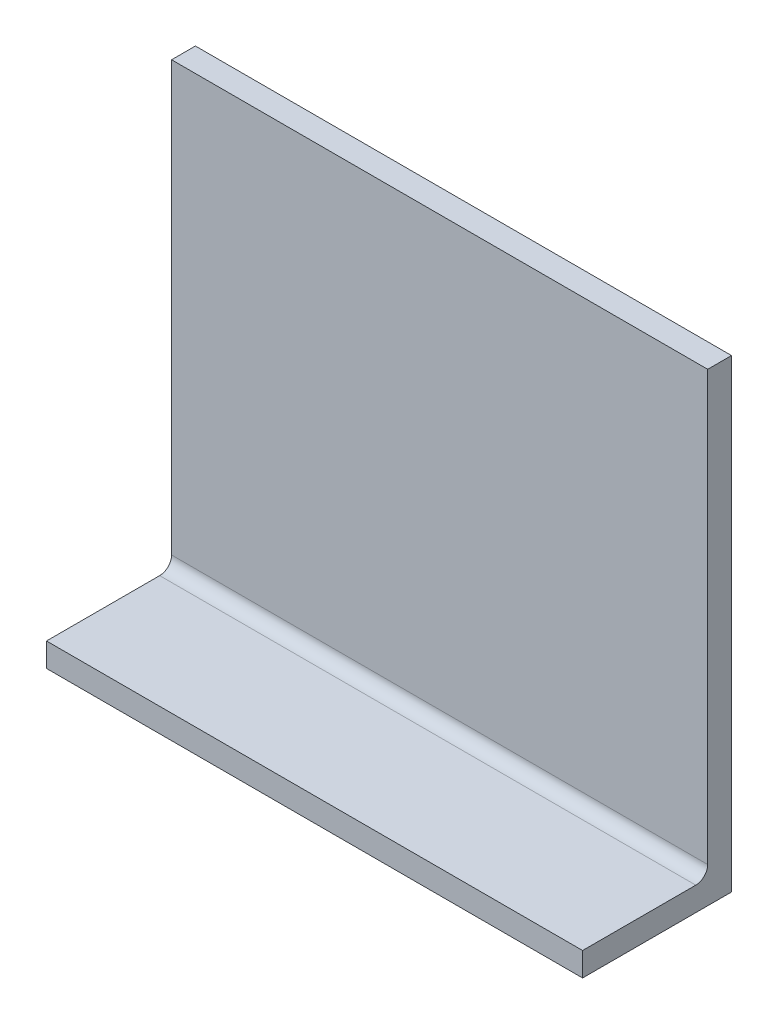
SolidWorks part; units mm, degrees
ref_plane "Front Plane" through (0, 0, 0) normal (0, 0, 1) x (1, 0, 0)
ref_plane "Top Plane" through (0, 0, 0) normal (0, 1, 0) x (1, 0, 0)
ref_plane "Right Plane" through (0, 0, 0) normal (1, 0, 0) x (0, 0, -1)
sketch "Sketch1" plane through (0, 0, 0) normal (0, 1, 0) x (1, 0, 0)
  line L1 (0, 0) -> (45, 0)
  line L2 (0, 0) -> (0, 12.5)
  line L3 (0, 12.5) -> (45, 12.5)
  line L4 (45, 0) -> (45, 12.5)
  dimension "D1" = 12.5
  dimension "D2" = 45
extrude "Boss-Extrude1" add sketch "Sketch1" along normal blind 2
sketch "Sketch2" plane through (0, 0, -12.5) normal (0, 0, -1) x (-1, 0, 0)
  line L1 (-45, 2) -> (0, 2)
  line L2 (-45, 2) -> (-45, 39)
  line L3 (-45, 39) -> (0, 39)
  line L4 (0, 2) -> (0, 39)
  dimension "D1" = 37
extrude "Boss-Extrude2" add sketch "Sketch2" against normal blind 2
fillet "Fillet1" radius 1 1 edges at (22.5, 2, -10.5)
